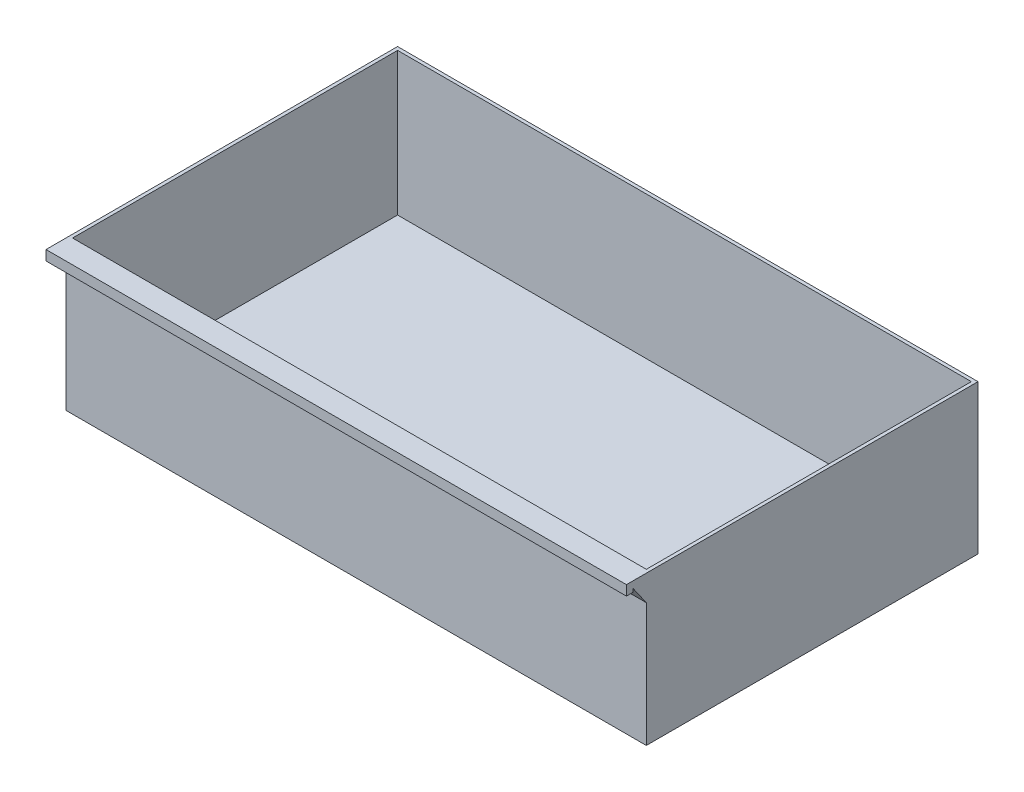
SolidWorks part; units mm, degrees
material "AISI 4130 Steel, normalized at 870C"
ref_plane "Front Plane" through (0, 0, 0) normal (0, 0, 1) x (1, 0, 0)
ref_plane "Top Plane" through (0, 0, 0) normal (0, 1, 0) x (1, 0, 0)
ref_plane "Right Plane" through (0, 0, 0) normal (1, 0, 0) x (0, 0, -1)
sketch "Sketch3" plane through (0, 0, 0) normal (0, 1, 0) x (1, 0, 0)
  line L1 (111.125, -63.5) -> (-111.125, -63.5)
  line L2 (111.125, -63.5) -> (111.125, 63.5)
  line L3 (111.125, 63.5) -> (-111.125, 63.5)
  line L5 (111.125, -63.5) -> (-111.125, 63.5) construction
  line L6 (111.125, 63.5) -> (-111.125, -63.5) construction
  line L10 (-111.125, 63.5) -> (-111.125, -63.5)
  point P0 (0, 0)
  dimension "D1" = 222.25
  dimension "D2" = 127
extrude "lower drawer" add sketch "Sketch3" along normal blind 57.15
sketch "Sketch6" plane through (0, 57.15, 0) normal (0, 1, 0) x (1, 0, 0)
  line L8 (-109.855, 62.23) -> (-109.855, -62.23)
  line L9 (-109.855, -62.23) -> (109.855, -62.23)
  line L10 (109.855, -62.23) -> (109.855, 62.23)
  line L11 (109.855, 62.23) -> (-109.855, 62.23)
  line L12 (-109.855, 62.23) -> (-109.855, -62.23)
  line L13 (-109.855, -62.23) -> (109.855, -62.23)
  line L14 (109.855, -62.23) -> (109.855, 62.23)
  line L15 (109.855, 62.23) -> (-109.855, 62.23)
  dimension "D1" = 1.27
extrude "Cut-Extrude1" cut sketch "Sketch6" against normal blind 54.61
sketch "Sketch10" plane through (-111.125, 0, 0) normal (-1, 0, 0) x (0, 0, 1)
  line L0 (63.5, 57.15) -> (71.12, 57.15)
  line L1 (71.12, 57.15) -> (71.12, 53.34)
  line L2 (71.12, 53.34) -> (68.58, 53.34)
  line L3 (68.58, 53.34) -> (68.58, 54.61)
  line L4 (68.58, 54.61) -> (63.5, 47.355)
  line L5 (63.5, 57.15) -> (63.5, 0) construction
  line L6 (63.5, 47.355) -> (63.5, 57.15)
  dimension "D1" = 7.62
  dimension "D2" = 3.81
  dimension "D3" = 2.54
  dimension "D4" = 35
  dimension "D5" = 2.54
extrude "handle" add sketch "Sketch10" against normal up to surface (222.25 mm away) up to face at (111.125, 28.575, 0)
